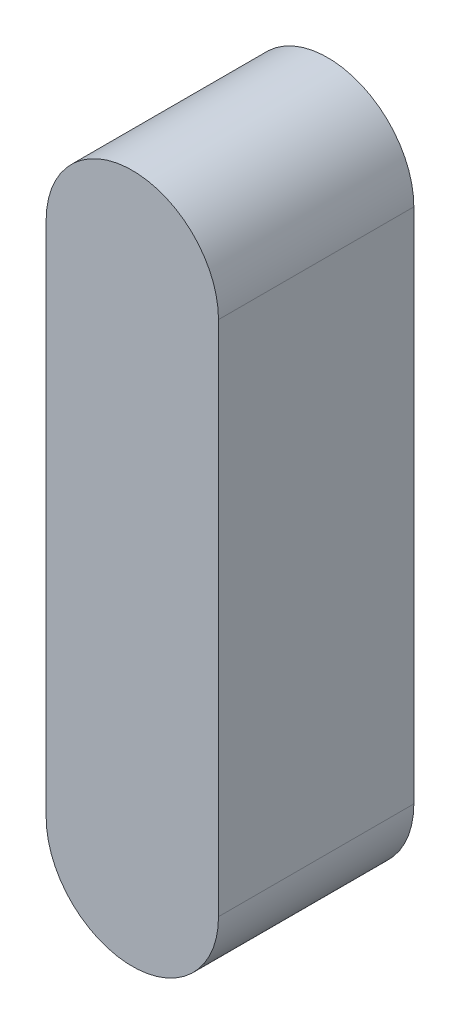
SolidWorks part; units mm, degrees
ref_plane "Front Plane" through (0, 0, 0) normal (0, 0, 1) x (1, 0, 0)
ref_plane "Top Plane" through (0, 0, 0) normal (0, 1, 0) x (1, 0, 0)
ref_plane "Right Plane" through (0, 0, 0) normal (1, 0, 0) x (0, 0, -1)
sketch "Finger_Skeleton" plane through (0, 0, 0) normal (0, 0, -1) x (-1, 0, 0)
  line L0 (0, 0) -> (0, 45)
  line L1 (0, 45) -> (0, 70)
  line L2 (0, 70) -> (0, 93)
  circle A1 centre (0, 0) radius 5 construction
  circle A2 centre (0, 45) radius 5 construction
  circle A3 centre (0, 70) radius 5 construction
  point P3 (0, 0)
  point P9 (0, 0)
  dimension "D4" = 10
  dimension "D5" = 10
  dimension "D6" = 10
  dimension "D1" = 45
  dimension "D2" = 25
  dimension "D3" = 23
sketch "Link1_Outline" plane through (0, 0, 0) normal (0, 0, 1) x (1, 0, 0)
  line L0 (0, 0) -> (0, 45) construction
  line L1 (-7.5, 0) -> (-7.5, 45)
  line L2 (7.5, 0) -> (7.5, 45)
  arc A0 (-7.5, 0) -> (7.5, 0) centre (0, 0) ccw
  arc A1 (7.5, 45) -> (-7.5, 45) centre (0, 45) ccw
  point P4 (0, 22.5)
  dimension "D1" = 15
extrude "Link1_Body" add sketch "Link1_Outline" along normal mid plane 17
